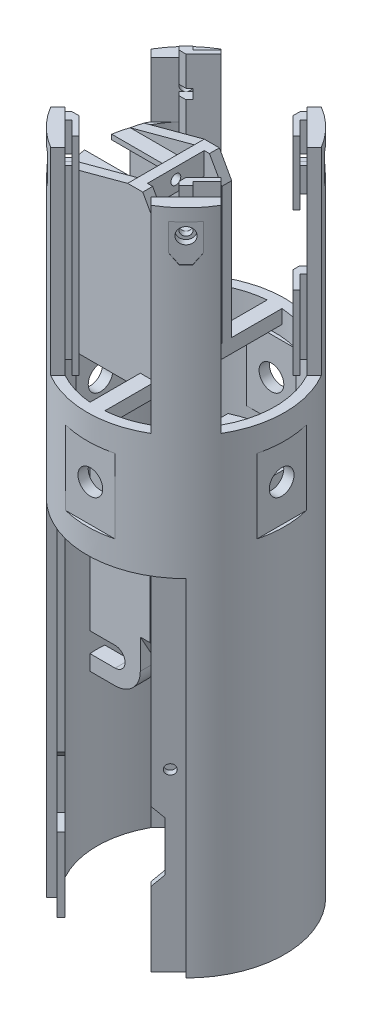
SolidWorks part; units mm, degrees
ref_plane "前视基准面" through (0, 0, 0) normal (0, 0, 1) x (1, 0, 0)
ref_plane "上视基准面" through (0, 0, 0) normal (0, 1, 0) x (1, 0, 0)
ref_plane "右视基准面" through (0, 0, 0) normal (1, 0, 0) x (0, 0, -1)
other "Configuration Table"
sketch "草图1" plane through (0, 0, 0) normal (0, 1, 0) x (1, 0, 0)
  circle A0 centre (0, 0) radius 20
  circle A1 centre (0, 0) radius 18
  dimension "D1" = 40
  dimension "D2" = 36
extrude "凸台-拉伸1" add sketch "草图1" along normal blind 25
sketch "草图2" plane through (0, 0, 0) normal (0, 1, 0) x (1, 0, 0)
  line L0 (-1000, 0) -> (49000, 0) construction
  line L1 (-17.9374, 1.5) -> (-17.9374, -1.5) construction
  line L2 (-17.9374, 1.5) -> (17.9374, 1.5)
  line L3 (-17.9374, -1.5) -> (17.9374, -1.5)
  circle A0 centre (0, 0) radius 18 construction
  arc A2 (-17.9374, 1.5) -> (-17.9374, -1.5) centre (0, 0) ccw
  arc A3 (17.9374, -1.5) -> (17.9374, 1.5) centre (0, 0) ccw
  point P8 (-17.9374, 0)
  dimension "D1" = 3
extrude "凸台-拉伸2" add sketch "草图2" along normal blind 2.8 from surface starting at face at (0, 0, 20)
sketch "草图3" plane through (0, 0, 0) normal (0, 1, 0) x (1, 0, 0)
  line L0 (0, -1000) -> (0, 49000) construction
  line L2 (7.75, 16.2462) -> (7.75, -1.5)
  line L3 (17.9374, -1.5) -> (-17.9374, -1.5) construction
  line L4 (7.75, -1.5) -> (-7.75, -1.5)
  line L5 (-7.75, -1.5) -> (-7.75, 16.2462)
  arc A0 (7.75, 16.2462) -> (-7.75, 16.2462) centre (0, 0) ccw
  point P9 (0, 16.2462)
  dimension "D1" = 15.5
  dimension "D2" = 15.5
  dimension "D3" = 17.7462
extrude "凸台-拉伸3" add sketch "草图3" along normal up to surface (2.8 mm away) up to face at (0, 2.8, 0)
sketch "草图4" plane through (0, 0, 0) normal (0, 1, 0) x (1, 0, 0)
  line L0 (7.75, 16.2462) -> (7.75, 2.0569)
  line L1 (-7.75, 16.2462) -> (-7.75, 2.0569)
  line L2 (5.75, 17.0569) -> (5.75, 4.0569)
  line L3 (-5.75, 17.0569) -> (-5.75, 4.0569)
  line L4 (5.75, 4.0569) -> (-5.75, 4.0569)
  line L5 (5.75, 2.0569) -> (-5.75, 2.0569)
  line L6 (-7.75, 2.0569) -> (-7.75, -1.5)
  line L7 (17.9374, -1.5) -> (-17.9374, -1.5) construction
  line L8 (-7.75, -1.5) -> (-5.75, -1.5)
  line L9 (-5.75, -1.5) -> (-5.75, 2.0569)
  line L10 (5.75, 2.0569) -> (5.75, -1.5)
  line L11 (5.75, -1.5) -> (7.75, -1.5)
  line L12 (7.75, -1.5) -> (7.75, 2.0569)
  arc A0 (7.75, 16.2462) -> (5.75, 17.0569) centre (0, 0) ccw
  arc A1 (-5.75, 17.0569) -> (-7.75, 16.2462) centre (0, 0) ccw
  dimension "D1" = 2
  dimension "D2" = 2
  dimension "D3" = 13
  dimension "D4" = 2
extrude "凸台-拉伸4" add sketch "草图4" against normal blind 32 from surface starting at face at (-11.8011, 0, -6.8681)
sketch "草图5" plane through (0, 0, 0) normal (0, 0, 1) x (1, 0, 0)
  line L0 (5.75, 0) -> (-5.75, -32) construction
  line L1 (5.75, -32) -> (-5.75, 0) construction
  line L2 (0, -2.2) -> (0, -29.8) construction
  line L3 (-5.75, -4.5) -> (5.75, -4.5)
  line L4 (-5.75, -4.5) -> (-5.75, -27.5)
  line L5 (-5.75, -27.5) -> (5.75, -27.5)
  line L6 (5.75, -4.5) -> (5.75, -27.5)
  line L7 (-5.75, -4.5) -> (5.75, -27.5) construction
  line L8 (-5.75, -27.5) -> (5.75, -4.5) construction
  circle A0 centre (0, -2.2) radius 1
  circle A1 centre (0, -29.8) radius 1
  point P8 (0, -16)
  point P17 (0, -16)
  dimension "D4" = 2
  dimension "D5" = 2
  dimension "D1" = 23
  dimension "D2" = 11.5
  dimension "D3" = 27.6
extrude "切除-拉伸1" cut sketch "草图5" against normal blind 32
sketch "草图6" plane through (0, 0, 0) normal (0, 1, 0) x (1, 0, 0)
  line L0 (5.75, 17.0569) -> (5.75, 4.0569)
  line L1 (-5.75, 4.0569) -> (5.75, 4.0569) construction
  line L2 (5.75, 4.0569) -> (5.75, 17.0569) construction
  line L3 (2.75, 4.0569) -> (2.75, 17.7887)
  line L4 (-5.75, 17.0569) -> (-5.75, 4.0569)
  line L5 (-5.75, 4.0569) -> (5.75, 4.0569) construction
  line L6 (-2.75, 4.0569) -> (-2.75, 17.7887)
  line L7 (2.75, 4.0569) -> (5.75, 4.0569)
  line L8 (-5.75, 4.0569) -> (-2.75, 4.0569)
  arc A0 (5.75, 17.0569) -> (2.75, 17.7887) centre (0, 0) ccw
  arc A1 (-2.75, 17.7887) -> (-5.75, 17.0569) centre (0, 0) ccw
  dimension "D1" = 3
  dimension "D2" = 3
extrude "凸台-拉伸5" add sketch "草图6" against normal blind 1 from surface starting at face at (0, -27.5, -3.0569)
sketch "草图7" plane through (0, 0, 0) normal (0, 1, 0) x (1, 0, 0)
  line L3 (2.75, 17.7887) -> (2.75, 4.0569)
  line L4 (5.75, 4.0569) -> (5.75, 17.0569)
  line L5 (2.75, 4.0569) -> (5.75, 4.0569)
  line L6 (2.75, 17.7887) -> (2.75, 4.0569)
  line L7 (5.75, 4.0569) -> (5.75, 17.0569)
  line L8 (2.75, 4.0569) -> (5.75, 4.0569)
  line L9 (-5.75, 17.0569) -> (-5.75, 4.0569)
  line L10 (-2.75, 4.0569) -> (-2.75, 17.7887)
  line L11 (-5.75, 4.0569) -> (-2.75, 4.0569)
  line L12 (-5.75, 17.0569) -> (-5.75, 4.0569)
  line L13 (-2.75, 4.0569) -> (-2.75, 17.7887)
  line L14 (-5.75, 4.0569) -> (-2.75, 4.0569)
  arc A1 (5.75, 17.0569) -> (2.75, 17.7887) centre (0, 0) ccw
  arc A2 (5.75, 17.0569) -> (2.75, 17.7887) centre (0, 0) ccw
  arc A3 (-2.75, 17.7887) -> (-5.75, 17.0569) centre (0, 0) ccw
  arc A4 (-2.75, 17.7887) -> (-5.75, 17.0569) centre (0, 0) ccw
  dimension "D1" = 0
  dimension "D2" = 0
extrude "凸台-拉伸6" add sketch "草图7" along normal blind 1 from surface starting at face at (0, -4.5, -3.0569)
sketch "草图8" plane through (0, 0, 0) normal (0, 1, 0) x (1, 0, 0)
  line L0 (-2.75, 17.7887) -> (-2.75, 4.0569) construction
  line L1 (2.75, 4.0569) -> (2.75, 17.7887) construction
  line L2 (-2.75, 17.7887) -> (-2.75, 4.0569)
  line L3 (2.75, 4.0569) -> (2.75, 17.7887)
  line L4 (2.75, 4.0569) -> (-2.75, 4.0569)
  arc A0 (2.75, 17.7887) -> (-2.75, 17.7887) centre (0, 0) ccw
extrude "切除-拉伸2" cut sketch "草图8" along normal up to surface (2.8 mm away) from surface up to face at (0, 2.8, -4.6558) starting at face at (0, 0, 20)
sketch "草图9" plane through (0, 0, 0) normal (1, 0, 0) x (0, 0, -1)
  line L0 (-1.5, -32) -> (-1.5, -27.5)
  line L1 (-1.5, -32) -> (-1.5, 0) construction
  line L2 (-1.5, -32) -> (1, -32)
  line L3 (-1.5, -32) -> (16.2462, -32) construction
  line L4 (1, -32) -> (-1.5, -27.5)
  line L5 (17.0569, -32) -> (4.0569, -32)
  line L6 (4.0569, -32) -> (17.0569, -28.5)
  line L7 (17.0569, -28.5) -> (17.0569, -32)
  dimension "D1" = 4.5
  dimension "D2" = 13
  dimension "D3" = 2.5
extrude "切除-拉伸3" cut sketch "草图9" against normal through all and the other way through all contours L7 L5 L6 | L4 L0 L2
sketch "草图10" plane through (0, 0, 0) normal (0, 1, 0) x (1, 0, 0)
  line L0 (0, -1000) -> (0, 49000) construction
  line L1 (-1.5, 17.9374) -> (1.5, 17.9374) construction
  line L2 (-1.5, 17.9374) -> (-1.5, -17.9374)
  line L3 (1.5, 17.9374) -> (1.5, -17.9374)
  arc A0 (1.5, 17.9374) -> (-1.5, 17.9374) centre (0, 0) ccw
  arc A1 (-1.5, -17.9374) -> (1.5, -17.9374) centre (0, 0) ccw
  point P9 (0, 17.9374)
  dimension "D1" = 3
extrude "凸台-拉伸7" add sketch "草图10" against normal blind 2.8 from surface starting at face at (0, 25, 20)
sketch "草图12" plane through (0, 0, 0) normal (0, 1, 0) x (1, 0, 0)
  line L0 (-1000, 0) -> (49000, 0) construction
  line L1 (-16.2462, -7.75) -> (-16.2462, 7.75) construction
  line L2 (-16.2462, 7.75) -> (1.5, 7.75)
  line L3 (1.5, 17.9374) -> (1.5, -17.9374) construction
  line L4 (1.5, 7.75) -> (1.5, -7.75)
  line L5 (1.5, -7.75) -> (-16.2462, -7.75)
  arc A0 (-16.2462, 7.75) -> (-16.2462, -7.75) centre (0, 0) ccw
  point P9 (-16.2462, 0)
  dimension "D1" = 15.5
extrude "凸台-拉伸8" add sketch "草图12" against normal up to surface (-22.2 mm away) from surface up to face at (0, 22.2, 0) starting at face at (9.75, 25, 0)
sketch "草图13" plane through (0, 0, 0) normal (0, 1, 0) x (1, 0, 0)
  line L0 (-1000, 0) -> (49000, 0) construction
  line L1 (-16.2462, 7.75) -> (-16.2462, -7.75) construction
  line L2 (-16.2462, 7.75) -> (1.5, 7.75)
  line L3 (1.5, 17.9374) -> (1.5, -17.9374) construction
  line L4 (1.5, 7.75) -> (1.5, 5.75)
  line L5 (1.5, 5.75) -> (-2.0569, 5.75)
  line L6 (-16.2462, -7.75) -> (1.5, -7.75)
  line L7 (1.5, -7.75) -> (1.5, -5.75)
  line L8 (1.5, -5.75) -> (-2.0569, -5.75)
  line L9 (-4.0569, 5.75) -> (-4.0569, -5.75)
  line L10 (-2.0569, 5.75) -> (-2.0569, -5.75)
  line L11 (-4.0569, 5.75) -> (-17.0569, 5.75)
  line L12 (-4.0569, -5.75) -> (-17.0569, -5.75)
  arc A0 (-16.2462, 7.75) -> (-17.0569, 5.75) centre (0, 0) ccw
  arc A1 (-17.0569, -5.75) -> (-16.2462, -7.75) centre (0, 0) ccw
  point P9 (-16.2462, 0)
  point P18 (-7.3731, 7.75)
  dimension "D1" = 15.5
  dimension "D2" = 2
  dimension "D3" = 2
  dimension "D4" = 2
  dimension "D5" = 13
extrude "凸台-拉伸9" add sketch "草图13" along normal blind 32 from surface starting at face at (9.75, 25, 0)
sketch "草图14" plane through (0, 0, 0) normal (1, 0, 0) x (0, 0, -1)
  line L0 (5.75, 57) -> (-5.75, 25) construction
  line L1 (5.75, 25) -> (-5.75, 57) construction
  line L2 (0, 54.8) -> (0, 27.2) construction
  line L3 (-5.75, 52.5) -> (5.75, 52.5)
  line L4 (-5.75, 52.5) -> (-5.75, 29.5)
  line L5 (-5.75, 29.5) -> (5.75, 29.5)
  line L6 (5.75, 52.5) -> (5.75, 29.5)
  line L7 (-5.75, 52.5) -> (5.75, 29.5) construction
  line L8 (-5.75, 29.5) -> (5.75, 52.5) construction
  circle A0 centre (0, 54.8) radius 1
  circle A1 centre (0, 27.2) radius 1
  point P8 (0, 41)
  point P17 (0, 41)
  dimension "D4" = 2
  dimension "D5" = 2
  dimension "D1" = 23
  dimension "D2" = 11.5
  dimension "D3" = 27.6
extrude "切除-拉伸4" cut sketch "草图14" against normal blind 32
sketch "草图15" plane through (0, 0, 0) normal (0, 1, 0) x (1, 0, 0)
  line L0 (-17.0569, 5.75) -> (-4.0569, 5.75)
  line L1 (-4.0569, -5.75) -> (-4.0569, 5.75) construction
  line L2 (-4.0569, -5.75) -> (-4.0569, 5.75) construction
  line L3 (-4.0569, 5.75) -> (-4.0569, 2.75)
  line L4 (-4.0569, 2.75) -> (-17.7887, 2.75)
  line L5 (-4.0569, -5.75) -> (-4.0569, -2.75)
  line L6 (-4.0569, -2.75) -> (-17.7887, -2.75)
  line L7 (-4.0569, -5.75) -> (-17.0569, -5.75)
  line L8 (-17.0569, -5.75) -> (-4.0569, -5.75) construction
  arc A0 (-17.7887, -2.75) -> (-17.0569, -5.75) centre (0, 0) ccw
  arc A1 (-17.0569, 5.75) -> (-17.7887, 2.75) centre (0, 0) ccw
  dimension "D1" = 3
  dimension "D2" = 3
extrude "凸台-拉伸10" add sketch "草图15" against normal blind 1 from surface starting at face at (-3.0569, 29.5, 0)
sketch "草图16" plane through (0, 0, 0) normal (0, 1, 0) x (1, 0, 0)
  line L0 (-4.0569, 5.75) -> (-4.0569, 2.75)
  line L1 (-4.0569, -2.75) -> (-4.0569, -5.75)
  line L2 (-17.0569, -5.75) -> (-2.0569, -5.75) construction
  line L3 (-4.0569, -5.75) -> (-4.0569, 5.75) construction
  line L4 (-17.7887, 2.75) -> (-4.0569, 2.75) construction
  line L5 (-17.7887, 2.75) -> (-4.0569, 2.75)
  line L6 (-4.0569, -2.75) -> (-17.7887, -2.75) construction
  line L7 (-4.0569, -2.75) -> (-17.7887, -2.75)
  line L8 (-4.0569, 5.75) -> (-17.0569, 5.75)
  line L9 (-4.0569, -5.75) -> (-17.0569, -5.75)
  arc A0 (-17.7887, -2.75) -> (-17.0569, -5.75) centre (0, 0) ccw construction
  arc A1 (-17.7887, -2.75) -> (-17.0569, -5.75) centre (0, 0) ccw
  arc A2 (-17.0569, 5.75) -> (-17.7887, 2.75) centre (0, 0) ccw construction
  arc A3 (-17.0569, 5.75) -> (-17.7887, 2.75) centre (0, 0) ccw
extrude "凸台-拉伸11" add sketch "草图16" along normal blind 1 from surface contours L8 A3 L5 L0 | L7 A1 L9 L1 region at (-10.7643, 0, -4.2364) region at (-10.7643, 0, 4.2364) starting at face at (-3.0569, 52.5, 0)
sketch "草图17" plane through (0, 0, 0) normal (0, 1, 0) x (1, 0, 0)
  line L0 (-4.0569, -5.75) -> (-4.0569, 5.75) construction
  line L1 (-17.7887, -2.75) -> (-4.0569, -2.75) construction
  line L2 (-4.0569, 2.75) -> (-17.7887, 2.75) construction
  line L3 (-4.0569, -2.75) -> (-4.0569, 2.75)
  line L4 (-17.7887, -2.75) -> (-4.0569, -2.75)
  line L5 (-4.0569, 2.75) -> (-17.7887, 2.75)
  arc A0 (-17.7887, 2.75) -> (-17.7887, -2.75) centre (0, 0) ccw
extrude "切除-拉伸5" cut sketch "草图17" against normal up to surface (-22.2 mm away) from surface up to face at (-4.6558, 22.2, 0) starting at face at (0, 25, 20)
sketch "草图18" plane through (0, 0, 0) normal (0, 0, 1) x (1, 0, 0)
  line L0 (1.5, 57) -> (1.5, 52.5)
  line L1 (1.5, 57) -> (1.5, 25) construction
  line L2 (1.5, 52.5) -> (-1, 57)
  line L3 (1.5, 57) -> (-16.2462, 57) construction
  line L4 (-1, 57) -> (1.5, 57)
  line L5 (-17.0569, 53.5) -> (-4.0569, 57)
  line L6 (-4.0569, 57) -> (-17.0569, 57)
  line L7 (-17.0569, 57) -> (-17.0569, 53.5)
  dimension "D1" = 13
  dimension "D2" = 4.5
  dimension "D3" = 2.5
extrude "切除-拉伸6" cut sketch "草图18" against normal through all and the other way through all
sketch "草图19" plane through (0, 0, 0) normal (0, 0, 1) x (1, 0, 0)
  line L0 (20, 25) -> (-20, 0) construction
  line L1 (-20, 25) -> (20, 0) construction
  circle A0 centre (0, 12.5) radius 2.5
  dimension "D1" = 5
sketch "草图20" plane through (0, 0, 0) normal (1, 0, 0) x (0, 0, -1)
  line L0 (20, 25) -> (-20, 0) construction
  line L1 (-20, 25) -> (20, 0) construction
  circle A0 centre (0, 12.5) radius 2.5
  dimension "D1" = 5
sketch "草图21" plane through (0, 0, 0) normal (0, 1, 0) x (1, 0, 0)
  line L0 (0, -1000) -> (0, 49000) construction
  line L1 (-1000, 0) -> (49000, 0) construction
  line L2 (-17.2916, -5) -> (-17.2916, 5)
  line L3 (17.2916, -5) -> (17.2916, 5)
  line L4 (-5, 17.2916) -> (5, 17.2916)
  line L5 (-5, -17.2916) -> (5, -17.2916)
  arc A0 (-17.2916, 5) -> (-17.2916, -5) centre (0, 0) ccw
  arc A1 (17.2916, -5) -> (17.2916, 5) centre (0, 0) ccw
  arc A2 (5, 17.2916) -> (-5, 17.2916) centre (0, 0) ccw
  arc A3 (-5, -17.2916) -> (5, -17.2916) centre (0, 0) ccw
  point P11 (-17.2916, 0)
  point P16 (0, 17.2916)
  dimension "D1" = 10
  dimension "D2" = 10
extrude "凸台-拉伸12" add sketch "草图21" along normal blind 15 from offset 5
sketch "草图22" plane through (0, 0, 0) normal (0, 1, 0) x (1, 0, 0)
  line L0 (-1000, 0) -> (49000, 0) construction
  line L1 (0, -1000) -> (0, 49000) construction
  line L2 (-5, 19.3649) -> (5, 19.3649)
  line L3 (-19.3649, -5) -> (-19.3649, 5)
  line L4 (19.3649, -5) -> (19.3649, 5)
  line L5 (-5, -19.3649) -> (5, -19.3649)
  arc A0 (-19.3649, 5) -> (-19.3649, -5) centre (0, 0) ccw
  arc A1 (5, 19.3649) -> (-5, 19.3649) centre (0, 0) ccw
  arc A2 (19.3649, -5) -> (19.3649, 5) centre (0, 0) ccw
  arc A3 (-5, -19.3649) -> (5, -19.3649) centre (0, 0) ccw
  point P10 (0, 19.3649)
  point P13 (-19.3649, 0)
  dimension "D1" = 40
  dimension "D2" = 10
  dimension "D3" = 10
extrude "切除-拉伸9" cut sketch "草图22" along normal blind 15 from offset 5
extrude "切除-拉伸10" cut sketch "草图19" against normal through all and the other way through all
extrude "切除-拉伸11" cut sketch "草图20" against normal through all and the other way through all
sketch "草图24" plane through (0, 0, 0) normal (0, 1, 0) x (1, 0, 0)
  circle A0 centre (0, 0) radius 20
  circle A1 centre (0, 0) radius 18
  dimension "D1" = 40
extrude "凸台-拉伸14" add sketch "草图24" against normal blind 70
sketch "草图27" plane through (0, 0, 0) normal (0, 1, 0) x (1, 0, 0)
  line L0 (-707.1068, -707.1068) -> (34648.2323, 34648.2323) construction
  line L1 (707.1068, -707.1068) -> (-34648.2323, 34648.2323) construction
  line L2 (-14.1421, -14.1421) -> (-12.7279, -12.7279)
  line L3 (14.1421, -14.1421) -> (12.7279, -12.7279)
  line L4 (-12.7279, 12.7279) -> (-14.1421, 14.1421)
  line L5 (12.7279, 12.7279) -> (14.1421, 14.1421)
  circle A0 centre (0, 0) radius 20 construction
  arc A1 (-14.1421, -14.1421) -> (14.1421, -14.1421) centre (0, 0) ccw
  circle A2 centre (0, 0) radius 18 construction
  arc A3 (-12.7279, -12.7279) -> (12.7279, -12.7279) centre (0, 0) ccw
  arc A4 (14.1421, 14.1421) -> (-14.1421, 14.1421) centre (0, 0) ccw
  arc A5 (12.7279, 12.7279) -> (-12.7279, 12.7279) centre (0, 0) ccw
extrude "切除-拉伸13" cut sketch "草图27" along normal up to surface from surface up to face at (12.8593, 0, 0) starting at face at (0, -70, 18)
sketch "草图28" plane through (0, 0, 0) normal (0, 1, 0) x (1, 0, 0)
  line L3 (-7.75, 1.5) -> (-17.9374, 1.5)
  line L4 (-7.75, -1.5) -> (-7.75, 1.5)
  line L5 (-17.9374, -1.5) -> (-7.75, -1.5)
  line L6 (-7.75, 1.5) -> (-17.9374, 1.5)
  line L7 (-7.75, -1.5) -> (-7.75, 1.5)
  line L8 (-17.9374, -1.5) -> (-7.75, -1.5)
  line L9 (7.75, -1.5) -> (17.9374, -1.5)
  line L10 (7.75, 1.5) -> (7.75, -1.5)
  line L11 (17.9374, 1.5) -> (7.75, 1.5)
  line L12 (7.75, -1.5) -> (17.9374, -1.5)
  line L13 (7.75, 1.5) -> (7.75, -1.5)
  line L14 (17.9374, 1.5) -> (7.75, 1.5)
  arc A0 (-12.7279, 12.7279) -> (-12.7279, -12.7279) centre (0, 0) ccw construction
  arc A1 (-17.9374, 1.5) -> (-17.9374, -1.5) centre (0, 0) ccw
  arc A2 (-17.9374, 1.5) -> (-17.9374, -1.5) centre (0, 0) ccw
  arc A3 (-17.9374, 1.5) -> (-17.9374, -1.5) centre (0, 0) ccw
  arc A4 (12.7279, -12.7279) -> (12.7279, 12.7279) centre (0, 0) ccw construction
  arc A5 (17.9374, -1.5) -> (17.9374, 1.5) centre (0, 0) ccw
  arc A7 (17.9374, -1.5) -> (17.9374, 1.5) centre (0, 0) ccw
  arc A8 (17.9374, -1.5) -> (17.9374, 1.5) centre (0, 0) ccw
  dimension "D1" = 0
  dimension "D2" = 0
extrude "凸台-拉伸16" add sketch "草图28" against normal up to vertex (27.5 mm away) contours L12 A5 L14 L13 | L6 A2 L8 L7 region at (-12.8646, 0, 0) region at (12.8646, 0, 0) up to point (-7.75, -27.5, 1.5)
sketch "草图32" plane through (0, 0, 0) normal (0, 1, 0) x (1, 0, 0)
  line L0 (-1000, 0) -> (49000, 0) construction
  line L1 (0, -1000) -> (0, 49000) construction
  line L2 (-707.1068, -707.1068) -> (34648.2323, 34648.2323) construction
  line L3 (707.1068, -707.1068) -> (-34648.2323, 34648.2323) construction
  line L4 (-15.7626, -8.6915) -> (-8.6915, -15.7626)
  line L8 (16.6111, -9.54) -> (9.54, -16.6111)
  line L9 (-16.6111, -9.54) -> (-9.54, -16.6111)
  line L10 (-16.6111, -9.54) -> (-15.7626, -8.6915)
  line L11 (-9.54, -16.6111) -> (-8.6915, -15.7626)
  line L12 (16.6111, -9.54) -> (15.7626, -8.6915)
  line L13 (15.7626, -8.6915) -> (8.6915, -15.7626)
  line L14 (9.54, -16.6111) -> (8.6915, -15.7626)
  line L15 (16.6111, 9.54) -> (15.7626, 8.6915)
  line L16 (15.7626, 8.6915) -> (8.6915, 15.7626)
  line L17 (9.54, 16.6111) -> (8.6915, 15.7626)
  line L18 (16.6111, 9.54) -> (9.54, 16.6111)
  line L19 (-16.6111, 9.54) -> (-9.54, 16.6111)
  line L20 (-16.6111, 9.54) -> (-15.7626, 8.6915)
  line L21 (-15.7626, 8.6915) -> (-8.6915, 15.7626)
  line L22 (-9.54, 16.6111) -> (-8.6915, 15.7626)
  circle A0 centre (0, 0) radius 18 construction
  point P15 (-12.227, -12.227)
  point P19 (-12.7279, -12.7279)
  point P22 (-13.0755, -13.0755)
  dimension "D1" = 10
  dimension "D2" = 10
  dimension "D3" = 1.2
extrude "凸台-拉伸30" add sketch "草图32" against normal up to surface (70 mm away) from surface contours L9 L11 L4 L10 | L19 L22 L21 L20 | L18 L17 L16 L15 | L8 L14 L13 L12 up to face at (-16.2175, -70, 0) starting at face at (0, 25, 20)
sketch "草图33" plane through (0, 0, 0) normal (0, 1, 0) x (1, 0, 0)
  line L0 (-15.7626, -8.6915) -> (-15.7626, -10.1915)
  line L1 (-15.7626, -10.1915) -> (-14.2626, -10.1915)
  line L2 (-15.7626, -8.6915) -> (-8.6915, -15.7626) construction
  line L3 (-14.2626, -10.1915) -> (-15.7626, -8.6915)
  line L4 (0, -1000) -> (0, 49000) construction
  line L5 (14.2626, -10.1915) -> (15.7626, -8.6915)
  line L6 (15.7626, -10.1915) -> (14.2626, -10.1915)
  line L7 (15.7626, -8.6915) -> (15.7626, -10.1915)
  dimension "D1" = 1.5
extrude "切除-拉伸14" cut sketch "草图33" against normal blind 10 from offset 17 offset against normal yes
ref_plane "基准面1" through (0, 0, 0) normal (-0.7071, 0, 0.7071) x (0, -1, 0)
sketch "草图36" plane through (0, 0, 0) normal (-0.7071, 0, 0.7071) x (0, -1, 0)
  line L0 (70, 5) -> (48, 5) construction
  line L1 (70, 5) -> (0, 5) construction
  line L2 (43, 5) -> (53, 5)
  line L4 (53, 3) -> (43, 3)
  line L6 (53, 3) -> (55, 5)
  line L7 (55, 5) -> (53, 5)
  line L8 (43, 3) -> (41, 5)
  line L9 (70, 5) -> (-25, 5) construction
  line L10 (41, 5) -> (43, 5)
  point P8 (48, 5)
  dimension "D1" = 22
  dimension "D2" = 10
  dimension "D3" = 2
  dimension "D4" = 45
  dimension "D5" = 10
  dimension "D6" = 2
extrude "切除-拉伸19" cut sketch "草图36" against normal up to next from surface contours L2 L7 L6 L4 L8 L10 starting at face at (-11.3078, -35, 14.8433)
sketch "草图38" plane through (0, 0, 0) normal (-0.7071, 0, 0.7071) x (0, -1, 0)
  line L0 (70, -5) -> (48, -5) construction
  line L1 (70, -5) -> (0, -5) construction
  line L2 (43, -5) -> (53, -5)
  line L4 (53, -3) -> (43, -3)
  line L6 (43, -3) -> (41, -5)
  line L7 (41, -5) -> (43, -5)
  line L8 (53, -3) -> (55, -5)
  line L9 (55, -5) -> (53, -5)
  point P7 (48, -5)
  dimension "D1" = 22
  dimension "D2" = 10
  dimension "D3" = 2
  dimension "D4" = 10
  dimension "D5" = 45
  dimension "D6" = 2
extrude "切除-拉伸20" cut sketch "草图38" against normal up to next from surface starting at face at (11.5199, -18, -12.9341)
ref_plane "基准面2" through (0, 0, 0) normal (-0.7071, 0, -0.7071) x (0, -1, 0)
sketch "草图39" plane through (0, 0, 0) normal (-0.7071, 0, -0.7071) x (0, -1, 0)
  line L0 (70, -5) -> (48, -5) construction
  line L1 (70, -5) -> (27, -5) construction
  line L2 (43, -5) -> (53, -5)
  line L4 (53, -3) -> (43, -3)
  line L6 (53, -3) -> (55, -5)
  line L7 (55, -5) -> (53, -5)
  line L8 (43, -3) -> (41, -5)
  line L9 (41, -5) -> (43, -5)
  point P8 (48, -5)
  dimension "D1" = 22
  dimension "D2" = 10
  dimension "D3" = 2
  dimension "D4" = 10
  dimension "D5" = 135
  dimension "D6" = 2
extrude "切除-拉伸21" cut sketch "草图39" against normal up to next from surface contours L4 L8 L9 L2 L7 L6 starting at face at (-11.3078, -35, -14.8433)
sketch "草图40" plane through (0, 0, 0) normal (-0.7071, 0, -0.7071) x (0, -1, 0)
  line L0 (70, 5) -> (48, 5) construction
  line L1 (70, 5) -> (0, 5) construction
  line L2 (43, 5) -> (53, 5)
  line L4 (53, 3) -> (43, 3)
  line L6 (53, 3) -> (55, 5)
  line L7 (55, 5) -> (53, 5)
  line L8 (43, 3) -> (41, 5)
  line L9 (41, 5) -> (43, 5)
  point P8 (48, 5)
  dimension "D1" = 22
  dimension "D2" = 10
  dimension "D3" = 2
  dimension "D4" = 10
  dimension "D5" = 45
  dimension "D6" = 2
extrude "切除-拉伸22" cut sketch "草图40" against normal up to next from surface starting at face at (13.0722, -19.7778, 11.3818)
sketch "草图41" plane through (0, 0, 0) normal (-0.7071, 0, 0.7071) x (0, -1, 0)
  line L0 (70, 5) -> (32, 5) construction
  line L1 (41, 5) -> (0, 5) construction
  line L2 (32, 5) -> (32, 0) construction
  line L3 (0, 0) -> (70, 0) construction
  circle A0 centre (34.5, 2.25) radius 1
  dimension "D2" = 2
  dimension "D4" = 2.5
  dimension "D1" = 38
  dimension "D3" = 2.75
extrude "切除-拉伸23" cut sketch "草图41" along normal up to next
sketch "草图45" plane through (0, 0, 0) normal (-0.7071, 0, 0.7071) x (0, -1, 0)
  line L0 (70, 0) -> (70, -5) construction
  line L1 (41, -5) -> (0, -5) construction
  circle A0 centre (34.5, -2.25) radius 1
  dimension "D2" = 2
  dimension "D1" = 35.5
  dimension "D3" = 2.75
extrude "切除-拉伸28" cut sketch "草图45" against normal up to next
sketch "草图46" plane through (0, 0, 0) normal (-0.7071, 0, -0.7071) x (0, -1, 0)
  line L0 (70, 0) -> (70, -5) construction
  line L1 (70, 0) -> (0, 0) construction
  circle A0 centre (34.5, -2.25) radius 1
  dimension "D2" = 2
  dimension "D1" = 35.5
  dimension "D3" = 2.25
extrude "切除-拉伸29" cut sketch "草图46" along normal up to next
sketch "草图47" plane through (0, 0, 0) normal (-0.7071, 0, -0.7071) x (0, -1, 0)
  line L0 (70, 0) -> (0, 0) construction
  line L1 (70, 0) -> (70, 5) construction
  circle A0 centre (34.5, 2.25) radius 1
  dimension "D1" = 2
  dimension "D3" = 35.5
  dimension "D2" = 2.25
extrude "切除-拉伸30" cut sketch "草图47" against normal up to next
sketch "草图48" plane through (0, 0, 0) normal (0, 1, 0) x (1, 0, 0)
  line L0 (-1000, 0) -> (49000, 0) construction
  line L1 (0, -1000) -> (0, 49000) construction
  line L2 (-707.1068, -707.1068) -> (34648.2323, 34648.2323) construction
  line L3 (707.1068, -707.1068) -> (-34648.2323, 34648.2323) construction
  line L4 (8.6915, -15.7626) -> (15.7626, -8.6915) construction
  line L5 (-8.6915, -15.7626) -> (-15.7626, -8.6915) construction
  line L6 (-8.6915, 15.7626) -> (-15.7626, 8.6915) construction
  line L7 (8.6915, 15.7626) -> (15.7626, 8.6915) construction
  line L8 (8.6915, -15.7626) -> (15.7626, -8.6915)
  line L9 (-8.6915, -15.7626) -> (-15.7626, -8.6915)
  line L10 (-8.6915, 15.7626) -> (-15.7626, 8.6915)
  line L11 (8.6915, 15.7626) -> (15.7626, 8.6915)
  line L12 (8.6915, 15.7626) -> (10.1575, 17.2286)
  line L14 (17.2286, 10.1575) -> (15.7626, 8.6915)
  line L15 (-8.6915, 15.7626) -> (-10.1575, 17.2286)
  line L17 (-17.2286, 10.1575) -> (-15.7626, 8.6915)
  line L20 (-10.1575, -17.2286) -> (-8.6915, -15.7626)
  line L21 (-15.7626, -8.6915) -> (-17.2286, -10.1575)
  line L22 (15.7626, -8.6915) -> (17.2286, -10.1575)
  line L24 (10.1575, -17.2286) -> (8.6915, -15.7626)
  circle A0 centre (0, 0) radius 18 construction
  arc A1 (10.1575, -17.2286) -> (17.2286, -10.1575) centre (0, 0) ccw
  arc A2 (-17.2286, -10.1575) -> (-10.1575, -17.2286) centre (0, 0) ccw
  arc A3 (-10.1575, 17.2286) -> (-17.2286, 10.1575) centre (0, 0) ccw
  arc A4 (17.2286, 10.1575) -> (10.1575, 17.2286) centre (0, 0) ccw
  dimension "D1" = 40
  dimension "D2" = 10
extrude "凸台-拉伸31" add sketch "草图48" along normal blind 40 from surface starting at face at (-4.4792, 25, 0)
sketch "草图49" plane through (0, 0, 0) normal (0, 1, 0) x (1, 0, 0)
  line L0 (-1000, 0) -> (49000, 0) construction
  line L1 (0, -1000) -> (0, 49000) construction
  line L2 (-707.1068, -707.1068) -> (34648.2323, 34648.2323) construction
  line L10 (707.1068, -707.1068) -> (-34648.2323, 34648.2323) construction
  line L16 (-15.7626, -8.6915) -> (-8.6915, -15.7626) construction
  line L27 (8.6915, -15.7626) -> (15.7626, -8.6915) construction
  line L28 (15.7626, 8.6915) -> (8.6915, 15.7626) construction
  line L29 (-8.6915, 15.7626) -> (-15.7626, 8.6915) construction
  line L30 (-12.9341, -11.5199) -> (-8.6915, -15.7626) construction
  line L31 (11.5199, -12.9341) -> (15.7626, -8.6915) construction
  line L32 (15.7626, 8.6915) -> (8.6915, 15.7626) construction
  line L33 (-8.6915, 15.7626) -> (-12.9341, 11.5199) construction
  line L34 (-12.9341, 11.5199) -> (-11.5199, 12.9341)
  line L35 (-11.5199, 12.9341) -> (-10.8128, 12.227)
  line L36 (-10.8128, 12.227) -> (-7.9844, 15.0554)
  line L37 (-7.9844, 15.0554) -> (-7.2773, 14.3483)
  line L38 (-7.2773, 14.3483) -> (-10.8128, 10.8128)
  line L41 (-12.227, 10.8128) -> (-12.9341, 11.5199)
  line L42 (14.3483, 7.2773) -> (15.0554, 7.9844)
  line L43 (10.8128, 10.8128) -> (14.3483, 7.2773)
  line L46 (15.0554, 7.9844) -> (12.227, 10.8128)
  line L47 (12.227, 10.8128) -> (12.9341, 11.5199)
  line L48 (12.9341, 11.5199) -> (11.5199, 12.9341)
  line L49 (11.5199, 12.9341) -> (10.8128, 12.227)
  line L52 (-7.2773, -14.3483) -> (-10.8128, -10.8128)
  line L53 (-7.9844, -15.0554) -> (-7.2773, -14.3483)
  line L54 (-10.8128, -12.227) -> (-7.9844, -15.0554)
  line L55 (-11.5199, -12.9341) -> (-10.8128, -12.227)
  line L56 (-12.9341, -11.5199) -> (-11.5199, -12.9341)
  line L57 (-12.227, -10.8128) -> (-12.9341, -11.5199)
  line L58 (10.8128, -10.8128) -> (14.3483, -7.2773)
  line L61 (11.5199, -12.9341) -> (10.8128, -12.227)
  line L62 (12.9341, -11.5199) -> (11.5199, -12.9341)
  line L63 (12.227, -10.8128) -> (12.9341, -11.5199)
  line L64 (15.0554, -7.9844) -> (12.227, -10.8128)
  line L65 (14.3483, -7.2773) -> (15.0554, -7.9844)
  line L66 (-12.227, -10.8128) -> (-10.8128, -10.8128)
  line L67 (-12.227, 10.8128) -> (-10.8128, 10.8128)
  line L68 (10.8128, -12.227) -> (10.8128, -10.8128)
  line L69 (10.8128, 12.227) -> (10.8128, 10.8128)
  point P19 (-12.227, 12.227)
  dimension "D1" = 1
  dimension "D2" = 1
  dimension "D3" = 2
  dimension "D4" = 4
  dimension "D5" = 135
  dimension "D6" = 135
  dimension "D7" = 135
  dimension "D8" = 4
  dimension "D9" = 135
extrude "凸台-拉伸32" add sketch "草图49" along normal up to surface (40 mm away) from surface up to face at (-13.0723, 65, 13.0723) starting at face at (0, 25, -15.1109)
sketch "草图51" plane through (0, 0, 0) normal (0, 1, 0) x (1, 0, 0)
  line L0 (12.9341, -11.5199) -> (11.5199, -12.9341)
  line L1 (11.5199, 12.9341) -> (12.9341, 11.5199)
  line L10 (15.7626, 8.6915) -> (17.2286, 10.1575)
  line L11 (10.1575, 17.2286) -> (8.6915, 15.7626)
  line L12 (8.6915, 15.7626) -> (11.5199, 12.9341)
  line L13 (11.5199, 12.9341) -> (10.8128, 12.227)
  line L14 (10.8128, 12.227) -> (10.8128, 10.8128)
  line L15 (10.8128, 10.8128) -> (14.3483, 7.2773)
  line L16 (14.3483, 7.2773) -> (15.0554, 7.9844)
  line L17 (15.0554, 7.9844) -> (12.227, 10.8128)
  line L18 (12.227, 10.8128) -> (12.9341, 11.5199)
  line L19 (12.9341, 11.5199) -> (15.7626, 8.6915)
  line L23 (11.5199, 12.9341) -> (10.8128, 12.227)
  line L24 (10.8128, 12.227) -> (10.8128, 10.8128)
  line L25 (10.8128, 10.8128) -> (14.3483, 7.2773)
  line L26 (14.3483, 7.2773) -> (15.0554, 7.9844)
  line L27 (15.0554, 7.9844) -> (12.227, 10.8128)
  line L28 (12.227, 10.8128) -> (12.9341, 11.5199)
  line L30 (17.2286, -10.1575) -> (15.7626, -8.6915)
  line L31 (15.7626, -8.6915) -> (12.9341, -11.5199)
  line L32 (12.9341, -11.5199) -> (12.227, -10.8128)
  line L33 (12.227, -10.8128) -> (15.0554, -7.9844)
  line L34 (15.0554, -7.9844) -> (14.3483, -7.2773)
  line L35 (14.3483, -7.2773) -> (10.8128, -10.8128)
  line L36 (10.8128, -10.8128) -> (10.8128, -12.227)
  line L37 (10.8128, -12.227) -> (11.5199, -12.9341)
  line L38 (11.5199, -12.9341) -> (8.6915, -15.7626)
  line L39 (8.6915, -15.7626) -> (10.1575, -17.2286)
  line L42 (12.9341, -11.5199) -> (12.227, -10.8128)
  line L43 (12.227, -10.8128) -> (15.0554, -7.9844)
  line L44 (15.0554, -7.9844) -> (14.3483, -7.2773)
  line L45 (14.3483, -7.2773) -> (10.8128, -10.8128)
  line L46 (10.8128, -10.8128) -> (10.8128, -12.227)
  line L47 (10.8128, -12.227) -> (11.5199, -12.9341)
  arc A1 (17.2286, 10.1575) -> (10.1575, 17.2286) centre (0, 0) ccw
  arc A3 (10.1575, -17.2286) -> (17.2286, -10.1575) centre (0, 0) ccw
  dimension "D1" = 0
  dimension "D2" = 0
extrude "切除-拉伸31" cut sketch "草图51" against normal blind 25 from surface starting at face at (-11.4416, 65, 12.7272)
sketch "草图52" plane through (0, 0, 0) normal (0, 1, 0) x (1, 0, 0)
  line L0 (8.6915, 15.7626) -> (9.4245, 16.4956)
  line L1 (8.6915, 15.7626) -> (10.1575, 17.2286) construction
  line L5 (10.1575, -17.2286) -> (8.6915, -15.7626) construction
  line L7 (8.6915, -15.7626) -> (9.4245, -16.4956)
  line L8 (9.4245, 16.4956) -> (11.5199, 12.9341)
  line L9 (11.5199, 12.9341) -> (8.6915, 15.7626)
  line L10 (9.4245, -16.4956) -> (11.5199, -12.9341)
  line L11 (11.5199, -12.9341) -> (8.6915, -15.7626)
extrude "切除-拉伸32" cut sketch "草图52" along normal blind 5 and the other way blind 5 from offset 47
sketch "草图58" plane through (0, 0, 0) normal (0, 1, 0) x (1, 0, 0)
  line L0 (-12.9341, 11.5199) -> (-15.7626, 8.6915)
  line L1 (-16.2462, 7.75) -> (-15.4899, 7.75)
  line L2 (-16.2462, -7.75) -> (-15.4899, -7.75)
  line L3 (-4.0569, -7.75) -> (-16.2462, -7.75) construction
  line L4 (-12.9341, -11.5199) -> (-15.7626, -8.6915)
  arc A0 (-15.7626, 8.6915) -> (-16.2462, 7.75) centre (0, 0) ccw
  arc A1 (-12.9341, 11.5199) -> (-15.4899, 7.75) centre (0, 0) ccw
  arc A2 (-15.4899, -7.75) -> (-12.9341, -11.5199) centre (0, 0) ccw
  arc A3 (-16.2462, -7.75) -> (-15.7626, -8.6915) centre (0, 0) ccw
extrude "凸台-拉伸40" add sketch "草图58" along normal up to vertex and the other way blind 0.25 from surface up to point (-16.2462, 53.7183, -7.75) starting at face at (17.7478, 25, 0)
sketch "草图59" plane through (0, 0, 0) normal (0, 1, 0) x (1, 0, 0)
  line L0 (-11.5199, 12.9341) -> (-12.9341, 11.5199)
  line L1 (-12.9341, -11.5199) -> (-11.5199, -12.9341)
  line L10 (-15.7626, -8.6915) -> (-17.2286, -10.1575)
  line L11 (-10.1575, -17.2286) -> (-8.6915, -15.7626)
  line L12 (-8.6915, -15.7626) -> (-11.5199, -12.9341)
  line L13 (-11.5199, -12.9341) -> (-10.8128, -12.227)
  line L14 (-10.8128, -12.227) -> (-7.9844, -15.0554)
  line L15 (-7.9844, -15.0554) -> (-7.2773, -14.3483)
  line L16 (-7.2773, -14.3483) -> (-10.8128, -10.8128)
  line L17 (-10.8128, -10.8128) -> (-12.227, -10.8128)
  line L18 (-12.227, -10.8128) -> (-12.9341, -11.5199)
  line L19 (-12.9341, -11.5199) -> (-15.7626, -8.6915)
  line L23 (-11.5199, -12.9341) -> (-10.8128, -12.227)
  line L24 (-10.8128, -12.227) -> (-7.9844, -15.0554)
  line L25 (-7.9844, -15.0554) -> (-7.2773, -14.3483)
  line L26 (-7.2773, -14.3483) -> (-10.8128, -10.8128)
  line L27 (-10.8128, -10.8128) -> (-12.227, -10.8128)
  line L28 (-12.227, -10.8128) -> (-12.9341, -11.5199)
  line L30 (-17.2286, 10.1575) -> (-15.7626, 8.6915)
  line L31 (-15.7626, 8.6915) -> (-12.9341, 11.5199)
  line L32 (-12.9341, 11.5199) -> (-12.227, 10.8128)
  line L33 (-12.227, 10.8128) -> (-10.8128, 10.8128)
  line L34 (-10.8128, 10.8128) -> (-7.2773, 14.3483)
  line L35 (-7.2773, 14.3483) -> (-7.9844, 15.0554)
  line L36 (-7.9844, 15.0554) -> (-10.8128, 12.227)
  line L37 (-10.8128, 12.227) -> (-11.5199, 12.9341)
  line L38 (-11.5199, 12.9341) -> (-8.6915, 15.7626)
  line L39 (-8.6915, 15.7626) -> (-10.1575, 17.2286)
  line L42 (-12.9341, 11.5199) -> (-12.227, 10.8128)
  line L43 (-12.227, 10.8128) -> (-10.8128, 10.8128)
  line L44 (-10.8128, 10.8128) -> (-7.2773, 14.3483)
  line L45 (-7.2773, 14.3483) -> (-7.9844, 15.0554)
  line L46 (-7.9844, 15.0554) -> (-10.8128, 12.227)
  line L47 (-10.8128, 12.227) -> (-11.5199, 12.9341)
  arc A1 (-17.2286, -10.1575) -> (-10.1575, -17.2286) centre (0, 0) ccw
  arc A3 (-10.1575, 17.2286) -> (-17.2286, 10.1575) centre (0, 0) ccw
  dimension "D1" = 0
  dimension "D2" = 0
extrude "凸台-拉伸41" add sketch "草图59" along normal blind 2 from surface contours L0 L42 L43 L44 L45 L46 L47 | L23 L24 L25 L26 L27 L28 L1 starting at face at (-11.4416, 65, 12.7272)
sketch "草图60" plane through (0, 0, 0) normal (0, 1, 0) x (1, 0, 0)
  line L0 (10.8128, -10.8128) -> (10.8128, -12.227) construction
  line L1 (10.8128, -12.227) -> (11.5199, -12.9341) construction
  line L2 (11.5199, -12.9341) -> (12.9341, -11.5199) construction
  line L3 (12.9341, -11.5199) -> (12.227, -10.8128) construction
  line L4 (12.227, -10.8128) -> (15.0554, -7.9844) construction
  line L5 (15.0554, -7.9844) -> (14.3483, -7.2773) construction
  line L6 (14.3483, -7.2773) -> (10.8128, -10.8128) construction
  line L7 (15.0554, 7.9844) -> (12.227, 10.8128) construction
  line L8 (12.227, 10.8128) -> (12.9341, 11.5199) construction
  line L9 (12.9341, 11.5199) -> (11.5199, 12.9341) construction
  line L10 (11.5199, 12.9341) -> (10.8128, 12.227) construction
  line L11 (10.8128, 12.227) -> (10.8128, 10.8128) construction
  line L12 (10.8128, 10.8128) -> (14.3483, 7.2773) construction
  line L13 (14.3483, 7.2773) -> (15.0554, 7.9844) construction
  line L14 (10.8128, -10.8128) -> (10.8128, -12.227)
  line L15 (10.8128, -12.227) -> (11.5199, -12.9341)
  line L16 (11.5199, -12.9341) -> (12.9341, -11.5199)
  line L17 (12.9341, -11.5199) -> (12.227, -10.8128)
  line L18 (12.227, -10.8128) -> (15.0554, -7.9844)
  line L19 (15.0554, -7.9844) -> (14.3483, -7.2773)
  line L20 (14.3483, -7.2773) -> (10.8128, -10.8128)
  line L21 (15.0554, 7.9844) -> (12.227, 10.8128)
  line L22 (12.227, 10.8128) -> (12.9341, 11.5199)
  line L23 (12.9341, 11.5199) -> (11.5199, 12.9341)
  line L24 (11.5199, 12.9341) -> (10.8128, 12.227)
  line L25 (10.8128, 12.227) -> (10.8128, 10.8128)
  line L26 (10.8128, 10.8128) -> (14.3483, 7.2773)
  line L27 (14.3483, 7.2773) -> (15.0554, 7.9844)
extrude "凸台-拉伸42" add sketch "草图60" against normal blind 11 and the other way blind 2 from surface starting at face at (13.0723, 65, -13.0723)
sketch "草图61" plane through (0, 0, 0) normal (0, 1, 0) x (1, 0, 0)
  line L0 (-1000, 0) -> (49000, 0) construction
  line L1 (0, -1000) -> (0, 49000) construction
  line L2 (-707.1068, -707.1068) -> (34648.2323, 34648.2323) construction
  line L3 (707.1068, -707.1068) -> (-34648.2323, 34648.2323) construction
  line L4 (-15.799, 12.2634) -> (-12.2634, 15.799)
  line L5 (-707.1068, -707.1068) -> (34648.2323, 34648.2323) construction
  line L6 (15.799, 12.2634) -> (12.2634, 15.799)
  line L7 (15.799, -12.2634) -> (12.2634, -15.799)
  line L8 (-12.2634, -15.799) -> (-15.799, -12.2634)
  arc A1 (-12.2634, 15.799) -> (-15.799, 12.2634) centre (0, 0) ccw
  arc A2 (12.2634, 15.799) -> (15.799, 12.2634) centre (0, 0) cw
  arc A3 (12.2634, -15.799) -> (15.799, -12.2634) centre (0, 0) ccw
  arc A4 (-15.799, -12.2634) -> (-12.2634, -15.799) centre (0, 0) ccw
  point P15 (-14.0312, 14.0312)
  point P18 (14.0312, 14.0312)
  dimension "D2" = 20
  dimension "D1" = 5
extrude "切除-拉伸33" cut sketch "草图61" against normal blind 10 from surface starting at face at (-12.7905, 65, 12.7905)
sketch "草图62" plane through (0, 0, 0) normal (0, 1, 0) x (1, 0, 0)
  line L0 (15.799, -12.2634) -> (12.2634, -15.799) construction
  line L1 (-12.2634, -15.799) -> (-15.799, -12.2634) construction
  line L2 (12.2634, 15.799) -> (15.799, 12.2634) construction
  line L3 (-15.799, 12.2634) -> (-12.2634, 15.799) construction
  line L4 (15.799, -12.2634) -> (12.2634, -15.799)
  line L5 (-12.2634, -15.799) -> (-15.799, -12.2634)
  line L6 (12.2634, 15.799) -> (15.799, 12.2634)
  line L7 (-15.799, 12.2634) -> (-12.2634, 15.799)
  arc A0 (12.2634, -15.799) -> (15.799, -12.2634) centre (0, 0) ccw construction
  arc A1 (-15.799, -12.2634) -> (-12.2634, -15.799) centre (0, 0) ccw construction
  arc A2 (15.799, 12.2634) -> (12.2634, 15.799) centre (0, 0) ccw construction
  arc A3 (-12.2634, 15.799) -> (-15.799, 12.2634) centre (0, 0) ccw construction
  arc A4 (12.2634, -15.799) -> (15.799, -12.2634) centre (0, 0) ccw
  arc A5 (-15.799, -12.2634) -> (-12.2634, -15.799) centre (0, 0) ccw
  arc A6 (15.799, 12.2634) -> (12.2634, 15.799) centre (0, 0) ccw
  arc A7 (-12.2634, 15.799) -> (-15.799, 12.2634) centre (0, 0) ccw
extrude "凸台-拉伸43" add sketch "草图62" against normal blind 2.5 from surface starting at face at (-13.0516, 65, 13.0516)
sketch "草图63" plane through (0, 0, 0) normal (-0.7071, 0, 0.7071) x (0, -1, 0)
  line L0 (-55, 1) -> (-57, 2.5)
  line L1 (-62.5, 2.5) -> (-55, 2.5) construction
  line L2 (-62.5, 2.5) -> (-62.5, -2.5) construction
  line L3 (-62.5, -2.5) -> (-55, -2.5) construction
  line L4 (-55, 2.5) -> (-55, -2.5) construction
  line L5 (-55, -1) -> (-57, -2.5)
  line L6 (-55, 1) -> (-55, 2.5)
  line L7 (-55, -1) -> (-55, -2.5)
  line L8 (-55, 2.5) -> (-57, 2.5)
  line L9 (-55, -2.5) -> (-57, -2.5)
  dimension "D1" = 1.5
  dimension "D2" = 2
  dimension "D3" = 1.5
  dimension "D4" = 2
extrude "凸台-拉伸44" add sketch "草图63" along normal up to surface (0.1318 mm away) from surface up to face at (0, 45, 0) starting at face at (-14.0312, 58.75, 14.0312)
sketch "草图64" plane through (0, 0, 0) normal (-0.7071, 0, 0.7071) x (0, -1, 0)
  line L3 (-55, -1) -> (-57, -2.5)
  line L4 (-57, -2.5) -> (-55, -2.5)
  line L5 (-55, -2.5) -> (-55, -1)
  line L6 (-55, -1) -> (-57, -2.5)
  line L7 (-57, -2.5) -> (-55, -2.5)
  line L8 (-55, -2.5) -> (-55, -1)
  line L9 (-57, 2.5) -> (-55, 1)
  line L10 (-55, 2.5) -> (-57, 2.5)
  line L11 (-55, 1) -> (-55, 2.5)
  line L12 (-57, 2.5) -> (-55, 1)
  line L13 (-55, 2.5) -> (-57, 2.5)
  line L14 (-55, 1) -> (-55, 2.5)
  dimension "D1" = 0
  dimension "D2" = 0
extrude "凸台-拉伸45" add sketch "草图64" against normal up to surface (0.1318 mm away) from surface up to face at (-14.0871, 58.1672, 14.0871) starting at face at (14.0312, 58.75, -14.0312)
sketch "草图65" plane through (0, 0, 0) normal (-0.7071, 0, -0.7071) x (0, -1, 0)
  line L0 (-55, 2.5) -> (-55, 1)
  line L1 (-55, 2.5) -> (-55, -2.5) construction
  line L2 (-55, 1) -> (-57, 2.5)
  line L3 (-55, 2.5) -> (-62.5, 2.5) construction
  line L4 (-57, 2.5) -> (-55, 2.5)
  line L5 (-55, -2.5) -> (-55, -1)
  line L6 (-55, -2.5) -> (-55, 2.5) construction
  line L7 (-55, -1) -> (-57, -2.5)
  line L8 (-55, -2.5) -> (-62.5, -2.5) construction
  line L9 (-57, -2.5) -> (-55, -2.5)
  dimension "D1" = 1.5
  dimension "D2" = 2
  dimension "D3" = 1.5
  dimension "D4" = 2
extrude "凸台-拉伸46" add sketch "草图65" along normal up to surface from surface up to face at (14.0871, 58.1672, -14.0871) starting at face at (-14.0312, 58.75, -14.0312)
sketch "草图66" plane through (0, 0, 0) normal (-0.7071, 0, -0.7071) x (0, -1, 0)
  line L3 (-55, -2.5) -> (-55, -1)
  line L4 (-55, -1) -> (-57, -2.5)
  line L5 (-57, -2.5) -> (-55, -2.5)
  line L6 (-55, -2.5) -> (-55, -1)
  line L7 (-55, -1) -> (-57, -2.5)
  line L8 (-57, -2.5) -> (-55, -2.5)
  line L9 (-55, 1) -> (-55, 2.5)
  line L10 (-57, 2.5) -> (-55, 1)
  line L11 (-55, 2.5) -> (-57, 2.5)
  line L12 (-55, 1) -> (-55, 2.5)
  line L13 (-57, 2.5) -> (-55, 1)
  line L14 (-55, 2.5) -> (-57, 2.5)
  dimension "D1" = 0
  dimension "D2" = 0
extrude "凸台-拉伸47" add sketch "草图66" against normal up to surface (0.1318 mm away) from surface up to face at (-14.0871, 58.1672, -14.0871) starting at face at (14.0312, 58.75, 14.0312)
sketch "草图67" plane through (0, 0, 0) normal (-0.7071, 0, 0.7071) x (0, -1, 0)
  line L0 (-57, 2.5) -> (-62.5, 2.5) construction
  line L1 (-65, -1) -> (-53.7183, -1) construction
  line L2 (-62.5, -2.5) -> (-62.5, 2.5) construction
  line L3 (-59.0003, 1) -> (-60.9997, 1)
  line L4 (-59.0003, 1) -> (-59.0003, -1)
  line L5 (-59.0003, -1) -> (-60.9997, -1)
  line L6 (-60.9997, 1) -> (-60.9997, -1)
  line L7 (-57, -5.5203) -> (-57, 2.6114) construction
  arc A0 (-60.9997, 0.0247) -> (-60.9997, -0.0247) centre (-60, 0) ccw
  arc A1 (-59.0003, -0.0247) -> (-59.0003, 0.0247) centre (-60, 0) ccw
  dimension "D3" = 2
  dimension "D1" = 2.5
  dimension "D2" = 2.5
  dimension "D4" = 1.9994
  dimension "D5" = 2.0003
  dimension "D6" = 2
extrude "切除-拉伸37" cut sketch "草图67" along direction (0.7071, 0, -0.7071) on the side against the normal up to surface (2 mm away) from surface contours L3 L6 L5 L4 region at (0, 60, 0) up to face at (-9.045, 46, 12.5806) starting at face at (-11.3431, -34.5, 13.1109)
sketch "草图68" plane through (0, 0, 0) normal (-0.7071, 0, 0.7071) x (0, -1, 0)
  line L4 (-59.0003, 1) -> (-60.9997, 1)
  line L5 (-60.9997, 1) -> (-60.9997, -1)
  line L6 (-60.9997, -1) -> (-59.0003, -1)
  line L7 (-59.0003, -1) -> (-59.0003, 1)
  line L8 (-59.0003, 1) -> (-60.9997, 1)
  line L9 (-60.9997, 1) -> (-60.9997, -1)
  line L10 (-60.9997, -1) -> (-59.0003, -1)
  line L11 (-59.0003, -1) -> (-59.0003, 1)
  arc A0 (-59.0003, -0.0247) -> (-59.0003, 0.0247) centre (-60, 0) ccw construction
  arc A1 (-60.9997, 0.0247) -> (-60.9997, -0.0247) centre (-60, 0) ccw construction
  arc A2 (-59.0003, -0.0247) -> (-59.0003, 0.0247) centre (-60, 0) ccw
  arc A3 (-60.9997, 0.0247) -> (-60.9997, -0.0247) centre (-60, 0) ccw
  dimension "D1" = 0
extrude "切除-拉伸38" cut sketch "草图68" along normal up to surface (2 mm away) from surface contours L10 L11 L8 L9 region at (0, 60, 0) up to face at (12.5806, 60.5, -9.045) starting at face at (10.9989, 14.4211, -13.4552)
sketch "草图70" plane through (0, 0, 0) normal (-0.7071, 0, 0.7071) x (0, -1, 0)
  line L0 (-62.5, -2.5) -> (-62.5, 2.5) construction
  line L1 (-57, -2.5) -> (-62.5, -2.5) construction
  circle A0 centre (-60, 0) radius 1
  dimension "D1" = 2
  dimension "D2" = 2.5
  dimension "D3" = 2.5
extrude "切除-拉伸39" cut sketch "草图70" against normal through all and the other way through all
sketch "草图71" plane through (0, 0, 0) normal (-0.7071, 0, -0.7071) x (0, -1, 0)
  line L2 (-65, 1) -> (-54, 1) construction
  line L3 (-61, -1) -> (-59, -1)
  line L4 (-61, -1) -> (-61, 1)
  line L5 (-61, 1) -> (-59, 1)
  line L6 (-59, -1) -> (-59, 1)
  line L7 (-67, -5) -> (-54, -5) construction
  line L8 (-54, -1) -> (-54, 1) construction
  dimension "D1" = 4
  dimension "D2" = 5
  dimension "D4" = 2
extrude "切除-拉伸40" cut sketch "草图71" along normal up to surface (34.5832 mm away) from surface up to face at (-11.3431, -34.5, -13.1109) starting at face at (11.6969, 8.087, 12.7571)
sketch "草图72" plane through (0, 0, 0) normal (-0.7071, 0, -0.7071) x (0, -1, 0)
  line L0 (-57, 2.5) -> (-62.5, 2.5) construction
  line L1 (-62.5, -2.5) -> (-62.5, 2.5) construction
  circle A0 centre (-60, 0) radius 1
  dimension "D1" = 2
  dimension "D2" = 2.5
  dimension "D3" = 2.5
extrude "切除-拉伸41" cut sketch "草图72" against normal through all and the other way through all
sketch "草图73" plane through (0, 0, 0) normal (-0.7071, 0, 0.7071) x (0, -1, 0)
  circle A0 centre (-60, 0) radius 1.6
  dimension "D1" = 3.2
extrude "切除-拉伸42" cut sketch "草图73" against normal blind 1.3 from surface starting at face at (-13.3241, 60, 14.7383)
sketch "草图74" plane through (0, 0, 0) normal (-0.7071, 0, 0.7071) x (0, -1, 0)
  circle A0 centre (-60, 0) radius 1.6
  dimension "D1" = 3.2
extrude "切除-拉伸43" cut sketch "草图74" along normal blind 1.3 from surface starting at face at (13.3241, 60, -14.7383)
sketch "草图75" plane through (0, 0, 0) normal (-0.7071, 0, -0.7071) x (0, -1, 0)
  circle A0 centre (-60, 0) radius 1.6
  dimension "D1" = 3.2
extrude "切除-拉伸44" cut sketch "草图75" against normal blind 1.3 from surface starting at face at (-14.7383, 60, -13.3241)
sketch "草图76" plane through (0, 0, 0) normal (-0.7071, 0, -0.7071) x (0, -1, 0)
  circle A0 centre (-60, 0) radius 1.6
  dimension "D1" = 3.2
extrude "切除-拉伸45" cut sketch "草图76" along normal blind 1.3 from surface starting at face at (14.7383, 60, 13.3241)
sketch "草图84" plane through (0, 0, 0) normal (0, 0, 1) x (1, 0, 0)
  line L0 (7.75, -27.5) -> (17.9374, -27.5) construction
  line L1 (7.75, -27.5) -> (7.75, -32) construction
  line L3 (12.8437, -31.5) -> (18, -31.5)
  line L4 (7.75, -27.5) -> (7.75, -32) construction
  line L5 (12.8437, -38.5937) -> (18.0006, -38.5937)
  line L6 (18.0006, -38.5937) -> (18.0006, -35.5)
  line L7 (18.0006, -33.5) -> (17.9374, -33.5)
  line L8 (7.75, -33.5) -> (7.75, -27.5)
  line L9 (7.75, -27.5) -> (17.9374, -27.5)
  line L10 (17.9374, -27.5) -> (18, -27.5)
  line L11 (17.9374, -27.5) -> (18, -27.5) construction
  line L12 (18, -27.5) -> (18, -31.5)
  line L13 (12.8437, -35.5) -> (18.0006, -35.5)
  line L15 (0, -1000) -> (0, 49000) construction
  line L16 (-7.75, -27.5) -> (-7.75, -32) construction
  line L17 (-12.8437, -35.5) -> (-18.0006, -35.5)
  line L18 (-18, -27.5) -> (-18, -31.5)
  line L19 (-17.9374, -27.5) -> (-18, -27.5)
  line L20 (-7.75, -27.5) -> (-17.9374, -27.5)
  line L21 (-7.75, -33.5) -> (-7.75, -27.5)
  line L22 (-18.0006, -33.5) -> (-17.9374, -33.5)
  line L23 (-18.0006, -38.5937) -> (-18.0006, -35.5)
  line L24 (-12.8437, -38.5937) -> (-18.0006, -38.5937)
  line L25 (-12.8437, -31.5) -> (-18, -31.5)
  arc A0 (12.8437, -31.5) -> (12.8437, -35.5) centre (12.8437, -33.5) ccw
  arc A1 (7.75, -33.5) -> (12.8437, -38.5937) centre (12.8437, -33.5) ccw
  arc A2 (-7.75, -33.5) -> (-12.8437, -38.5937) centre (-12.8437, -33.5) cw
  arc A3 (-12.8437, -31.5) -> (-12.8437, -35.5) centre (-12.8437, -33.5) cw
  dimension "D1" = 4
  dimension "D4" = 0.0633
  dimension "D2" = 6
  dimension "D3" = 5.0937
  dimension "D5" = 0.0626
  dimension "D6" = 4
  dimension "D7" = 5.1569
extrude "凸台-拉伸56" add sketch "草图84" along normal up to surface (3 mm away) from surface contours L8 A1 L5 L6 L13 A0 L3 L12 L10 L9 | L25 A3 L17 L23 L24 A2 L21 L20 L19 L18 region at (10.6927, -33.5, 0) region at (-10.6927, -33.5, 0) up to face at (0, -15.94, 1.5) starting at face at (-12.8437, -12.35, -1.5)
equation "\"2.5、\"=2.0817"
